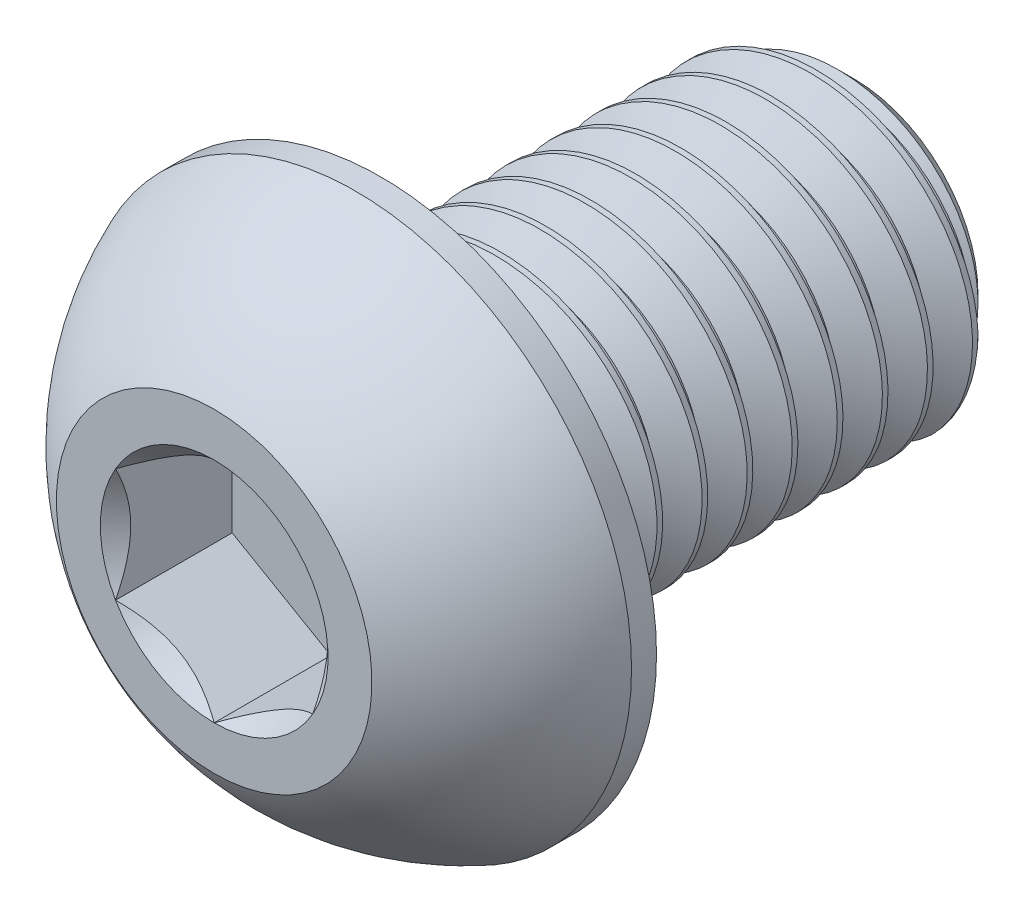
SolidWorks part; units mm, degrees
material "AISI 304"
ref_plane "Front" through (0, 0, 0) normal (0, 0, 1) x (1, 0, 0)
ref_plane "Top" through (0, 0, 0) normal (0, 1, 0) x (1, 0, 0)
ref_plane "Right" through (0, 0, 0) normal (1, 0, 0) x (0, 0, -1)
sketch "Sketch1" plane through (0, 0, 0) normal (1, 0, 0) x (0, 0, -1)
  line L2 (3.3528, 3.175) -> (12.8778, 3.175)
  line L3 (12.8778, 3.175) -> (12.8778, 0)
  line L4 (12.8778, 0) -> (3.3528, 0)
  line L6 (2.8499, 5.5499) -> (3.3528, 5.5499) construction
  line L7 (12.8778, 3.175) -> (12.8778, -3.175) construction
  line L8 (0, 0) -> (3.3528, 0) construction
  line L9 (3.3528, 5.5499) -> (3.3528, -5.5499) construction
  line L11 (3.3528, 3.175) -> (3.3528, 0)
  line L13 (0, 1.9844) -> (0, -1.9844) construction
  line L14 (0, 1.9844) -> (0, 3.175) construction
  arc A3 (0, 3.175) -> (2.8499, 5.5499) centre (5.0603, 0) cw construction
  dimension "D1" = 0.5029
revolve "Revolve1" add sketch "Sketch1" angle 360 mid plane about L4
sketch "Sketch3" plane through (0, 0, -12.8778) normal (0, 0, -1) x (-1, 0, 0)
  circle A0 centre (0, 0) radius 3.175
curve "Helix/Spiral1" pitch 0.9071 height 10.4321 radius 3.175 centre (0, 0, -12.8778) axis (0, 0, 1) start towards (0, 1, 0)
sketch "Sketch2" plane through (0, 0, 0) normal (1, 0, 0) x (0, 0, -1)
  line L0 (12.8778, 3.175) -> (13.6715, 3.175)
  line L1 (13.6715, 3.175) -> (13.3314, 2.5858)
  line L2 (13.3314, 2.5858) -> (13.218, 2.5858)
  line L3 (13.218, 2.5858) -> (12.8778, 3.175)
  line L4 (13.0479, 2.8804) -> (13.5015, 2.8804) construction
  dimension "D1" = 60
  dimension "D2" = 0.1134
  dimension "D3" = 0.4536
chamfer "Chamfer1" distance 0.6804 angle 45 1 edges at (0, 3.175, -12.8778)
sweep "Cut-Sweep1" cut profiles "Sketch2" path "Helix/Spiral1" align with end faces yes
sketch "Sketch7" plane through (0, 0, 0) normal (1, 0, 0) x (0, 0, -1)
  line L6 (2.8499, 5.5499) -> (3.3528, 5.5499) construction
  line L8 (0, 0) -> (3.3528, 0) construction
  line L11 (3.3528, 5.5499) -> (3.3528, -5.5499) construction
  line L12 (2.8499, 5.5499) -> (3.3528, 5.5499)
  line L13 (0, 0) -> (3.3528, 0)
  line L14 (0, 1.9844) -> (0, -1.9844) construction
  line L15 (3.3528, 5.5499) -> (3.3528, 0)
  line L16 (0, 3.175) -> (0, 0)
  arc A2 (2.8499, 5.5499) -> (0, 3.175) centre (5.0603, 0) ccw construction
  arc A3 (2.8499, 5.5499) -> (0, 3.175) centre (5.0603, 0) ccw
revolve "Revolve2" add sketch "Sketch7" angle 360 mid plane about L13
sketch "Sketch5" plane through (0, 0, 0) normal (0, 0, 1) x (1, 0, 0)
  line L1 (1.9844, -1.1457) -> (1.9844, 1.1457)
  line L2 (1.9844, 1.1457) -> (0, 2.2914)
  line L3 (0, 2.2914) -> (-1.9844, 1.1457)
  line L4 (-1.9844, 1.1457) -> (-1.9844, -1.1457)
  line L5 (-1.9844, -1.1457) -> (0, -2.2914)
  line L6 (0, -2.2914) -> (1.9844, -1.1457)
  circle A0 centre (0, 0) radius 1.9844 construction
extrude "Cut-Extrude2" cut sketch "Sketch5" against normal blind 2.347
sketch "Sketch6" plane through (0, 0, 0) normal (0, 0, 1) x (1, 0, 0)
  circle A0 centre (0, 0) radius 2.2914
extrude "Cut-Extrude3" cut sketch "Sketch6" against normal blind 2.347 draft 45
sketch "Sketch9" [suppressed] plane through (0, 0, -3.3528) normal (0, 0, 1) x (1, 0, 0)
  circle A2 centre (0, 0) radius 3.175
extrude "Boss-Extrude2" [suppressed] add sketch "Sketch9" against normal offset from surface (25.4 mm away) 22.225 up to face at (0, 2.4946, -12.8778)
sketch "Sketch10" plane through (0, 0, 0) normal (1, 0, 0) x (0, 0, -1)
  line L0 (12.8778, 3.175) -> (12.8778, -3.175) construction
  point P0 (11.5171, -3.175)
  dimension "D1" = 1.3607
equation "\"D3@Helix/Spiral1\" = \"Lg@Sketch1\" + \"D4@Helix/Spiral1\""
equation "\"D2@Sketch2\" = \"D4@Helix/Spiral1\" * .125"
equation "\"D3@Sketch2\" = \"D4@Helix/Spiral1\" * .5"
equation "\"D1@Chamfer1\" = \"D4@Helix/Spiral1\" * .75"
equation "\"D1@Cut-Extrude2\" = \"Head Ht@Sketch1\" * .7"
equation "\"D1@Sketch1\" = \"Head Ht@Sketch1\" * .15"
equation "\"D1@Sketch10\" = \"D4@Helix/Spiral1\" * 1.5"
equation "\"D1@Cut-Extrude3\" = \"D1@Cut-Extrude2\""
